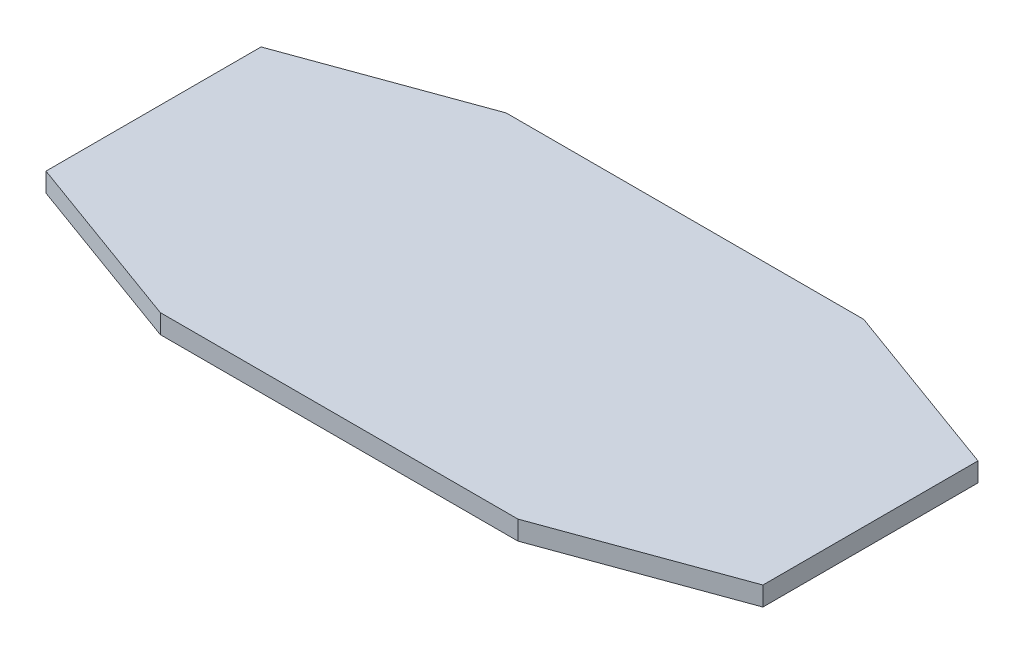
SolidWorks part; units mm, degrees
material "ABS"
ref_plane "Front Plane" through (0, 0, 0) normal (0, 0, 1) x (1, 0, 0)
ref_plane "Top Plane" through (0, 0, 0) normal (0, 1, 0) x (1, 0, 0)
ref_plane "Right Plane" through (0, 0, 0) normal (1, 0, 0) x (0, 0, -1)
sketch "Sketch1" plane through (0, 0, 0) normal (0, 1, 0) x (1, 0, 0)
  line L0 (-150, 0) -> (150, 0) construction
  line L1 (-150, 45) -> (-150, -45)
  line L2 (140.0883, -41.1583) -> (79.948, -63.0476) construction
  line L3 (-140.0883, 41.1583) -> (-142.4825, 47.7362) construction
  line L4 (-140.0883, 41.1583) -> (-79.948, 63.0476) construction
  line L5 (-150, 45) -> (-74.8246, 72.3616)
  line L6 (-79.948, 63.0476) -> (-82.3421, 69.6255) construction
  line L7 (-143, 32) -> (-143, -32) construction
  line L8 (-140.0883, -41.1583) -> (-142.4825, -47.7362) construction
  line L9 (-79.948, -63.0476) -> (-82.3421, -69.6255) construction
  line L10 (-140.0883, -41.1583) -> (-79.948, -63.0476) construction
  line L11 (-150, -45) -> (-74.8246, -72.3616)
  line L12 (0, 74.8501) -> (0, -82.9126) construction
  line L13 (79.948, -63.0476) -> (82.3421, -69.6255) construction
  line L14 (140.0883, -41.1583) -> (142.4825, -47.7362) construction
  line L15 (143, 32) -> (143, -32) construction
  line L16 (79.948, 63.0476) -> (82.3421, 69.6255) construction
  line L17 (140.0883, 41.1583) -> (79.948, 63.0476) construction
  line L18 (140.0883, 41.1583) -> (142.4825, 47.7362) construction
  line L19 (150, -45) -> (74.8246, -72.3616)
  line L20 (150, 45) -> (74.8246, 72.3616)
  line L21 (150, 45) -> (150, -45)
  line L22 (-74.8246, 72.3616) -> (74.8246, 72.3616)
  line L23 (-74.8246, -72.3616) -> (74.8246, -72.3616)
  point P0 (0, 0)
  point P3 (-150, 0)
  point P10 (-143, 0)
  point P13 (0, 0)
  point P37 (143, 0)
  dimension "D1" = 7
  dimension "D2" = 90
  dimension "D3" = 64
  dimension "D4" = 300
  dimension "D5" = 7
  dimension "D6" = 8
  dimension "D7" = 80
  dimension "D8" = 110
extrude "Boss-Extrude1" add sketch "Sketch1" along normal blind 8
